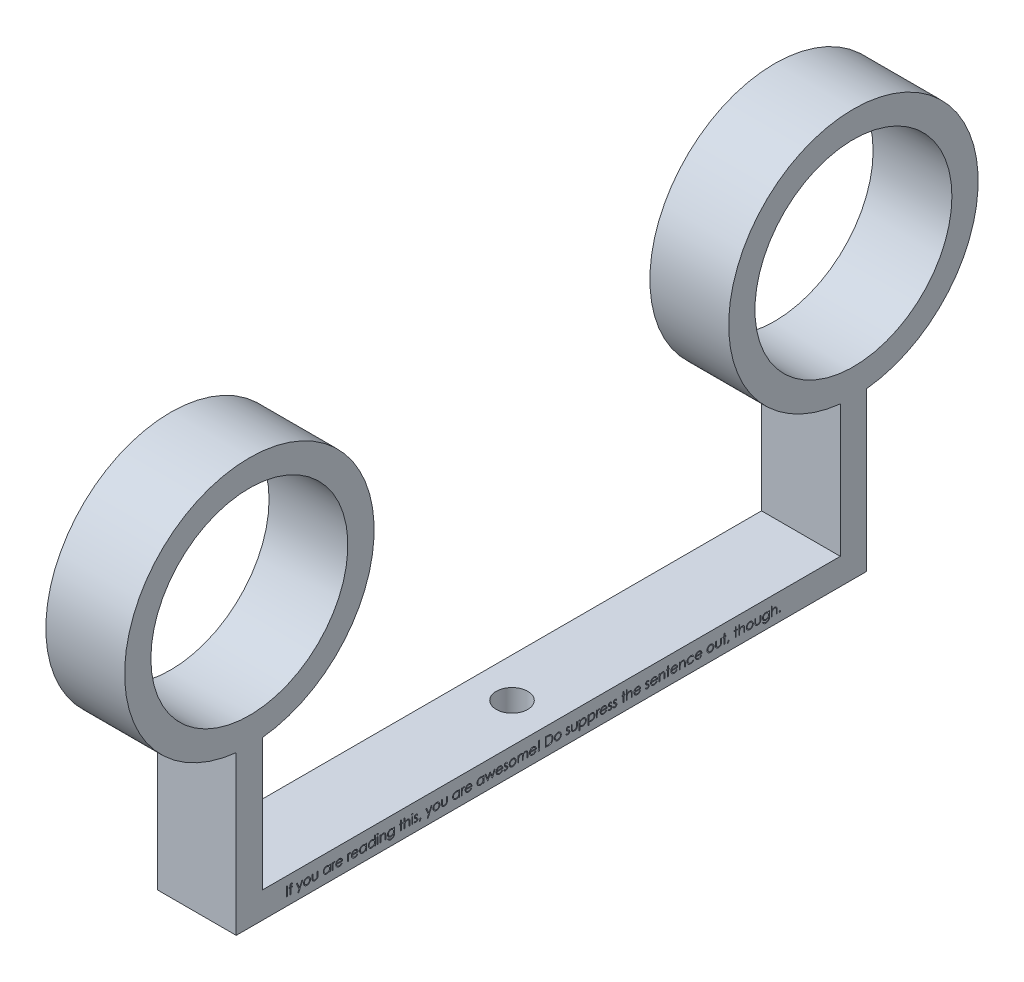
SolidWorks part; units mm, degrees
ref_plane "Front Plane" through (0, 0, 0) normal (0, 0, 1) x (1, 0, 0)
ref_plane "Top Plane" through (0, 0, 0) normal (0, 1, 0) x (1, 0, 0)
ref_plane "Right Plane" through (0, 0, 0) normal (1, 0, 0) x (0, 0, -1)
sketch "Sketch1" plane through (0, 0, 0) normal (1, 0, 0) x (0, 0, -1)
  line L0 (0, 150) -> (0, 0) construction
  line L1 (0, 0) -> (120, 0)
  line L2 (120, 0) -> (120, 70)
  dimension "D1" = 120
  dimension "D2" = 70
  dimension "D3" = 150
extrude "Extrude-Thin2" add sketch "Sketch1" along normal blind 30 thin thin type one direction reverse wall 10
sketch "Sketch2" plane through (30, 0, 0) normal (1, 0, 0) x (0, 0, -1)
  line L0 (110, 70) -> (120, 70) construction
  line L1 (115, 107.5) -> (115, 70) construction
  circle A0 centre (115, 107.5) radius 37.5
  point P7 (115, 70)
  dimension "D1" = 75
extrude "Extrude-Thin3" add sketch "Sketch2" against normal up to surface (30 mm away) thin up to face at (0, 26.6667, -76.6667) thin type one direction wall 10
mirror "Mirror1" about plane through (30, 0, 0) normal (0, 0, 1) of bodies 104
sketch "Sketch3" plane through (0, 10, 0) normal (0, 1, 0) x (1, 0, 0)
  line L0 (0, 0) -> (30, 0) construction
  line L1 (30, -110) -> (30, 110) construction
  circle A0 centre (15, 0) radius 6
  dimension "D1" = 12
extrude "Cut-Extrude1" cut sketch "Sketch3" against normal through all and the other way through all
sketch "Sketch6" plane through (30, 0, 0) normal (1, 0, 0) x (0, 0, -1)
  text T0 "If you are reading this, you are awesome! Do suppress the sentence out, though. "
extrude "Writing on the wall" cut sketch "Sketch6" against normal blind 1
sketch "Sketch7" plane through (0, 0, 0) normal (0, 0, 1) x (1, 0, 0)
  line L0 (15, 110) -> (15, 0) construction
  line L1 (30, 0) -> (0, 0) construction
  circle A0 centre (15, 110) radius 5
  dimension "D1" = 10
  dimension "D2" = 110
extrude "Support Rod" [suppressed] add sketch "Sketch7" along normal up to next and the other way up to next
